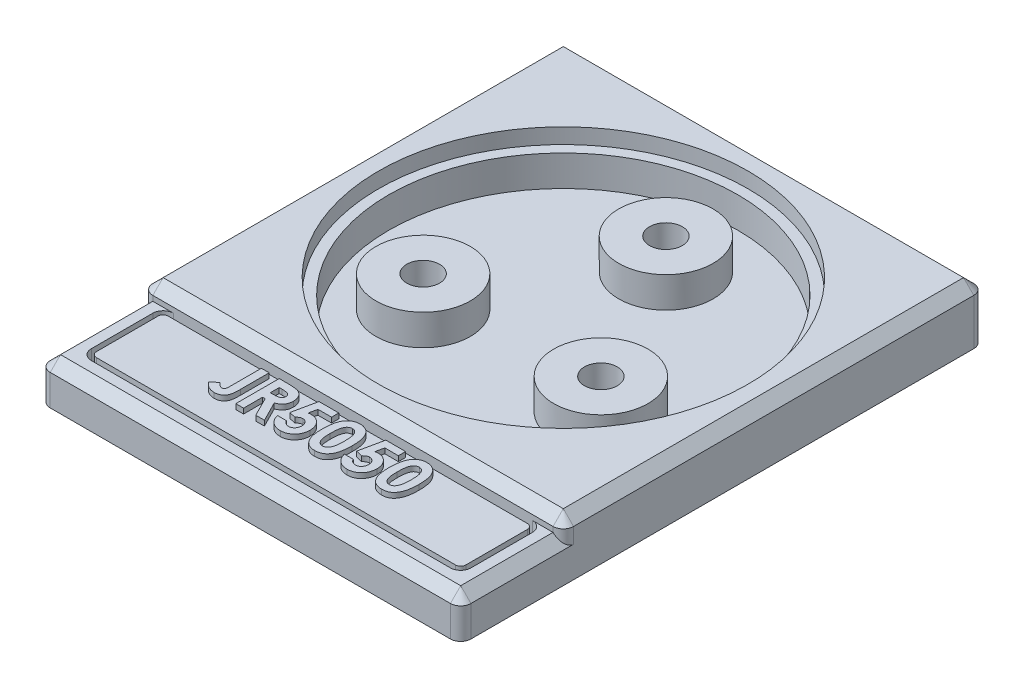
SolidWorks part; units mm, degrees
note: The reader was unsure of these and kept them because the rebuilt part matched: shared geometry of "Sketch3<3>", "Sketch3<4>".
other "Markup1"
sketch "Sketch7" plane through (-28, 7.5, 62.5) normal (-0.8225, 0.3134, 0.4747) x (0.5688, 0.4607, 0.6813)
material "PET"
ref_plane "Front Plane" through (0, 0, 0) normal (0, 0, 1) x (1, 0, 0)
ref_plane "Top Plane" through (0, 0, 0) normal (0, 1, 0) x (1, 0, 0)
ref_plane "Right Plane" through (0, 0, 0) normal (1, 0, 0) x (0, 0, -1)
sketch "base_sketch" plane through (0, 0, 0) normal (0, 1, 0) x (1, 0, 0)
  line L0 (0, 0) -> (0, 10) construction
  line L1 (-12.5, 12.5) -> (12.5, 12.5) construction
  line L2 (-12.5, 12.5) -> (-12.5, -12.5) construction
  line L3 (-12.5, -12.5) -> (12.5, -12.5) construction
  line L4 (12.5, 12.5) -> (12.5, -12.5) construction
  line L5 (-12.5, 12.5) -> (12.5, -12.5) construction
  line L6 (-12.5, -12.5) -> (12.5, 12.5) construction
  line L7 (-18, 18) -> (18, 18) construction
  line L8 (-18, 18) -> (-18, -18) construction
  line L9 (-18, -18) -> (18, -18) construction
  line L10 (18, 18) -> (18, -18) construction
  line L11 (-18, 18) -> (18, -18) construction
  line L12 (-18, -18) -> (18, 18) construction
  circle A0 centre (-12.5, 12.5) radius 1.6 construction
  circle A1 centre (12.5, 12.5) radius 1.6 construction
  circle A2 centre (-12.5, -12.5) radius 1.6 construction
  circle A3 centre (12.5, -12.5) radius 1.6 construction
  circle A4 centre (0, 0) radius 18 construction
  circle A5 centre (0, 10) radius 1.6 construction
  circle A6 centre (8.6603, -5) radius 1.6 construction
  circle A7 centre (-8.6603, -5) radius 1.6 construction
  point P0 (0, 0)
  point P11 (0, 0)
  point P20 (-10.4697, -3.1895)
  point P21 (0, 0)
  point P25 (0, 0)
  point P26 (0, 6.9336)
  dimension "D1" = 3.2
  dimension "D6" = 36
  dimension "D2" = 25
  dimension "D3" = 36
  dimension "D4" = 36
  dimension "D5" = 25
  dimension "D8" = 10
  dimension "D7" = 3
sketch "Sketch3" plane through (0, 0, 0) normal (0, 1, 0) x (1, 0, 0)
  line L14 (-17.5, -17.5) -> (17.5, -17.5)
  line L15 (17.5, -17.5) -> (17.5, 17.5)
  line L16 (17.5, 17.5) -> (-17.5, 17.5)
  line L17 (-17.5, 17.5) -> (-17.5, -17.5)
  line L18 (-17.5, -17.5) -> (17.5, -17.5) construction
  line L19 (17.5, -17.5) -> (17.5, 17.5) construction
  line L20 (17.5, 17.5) -> (-17.5, 17.5) construction
  line L21 (-17.5, 17.5) -> (-17.5, -17.5) construction
  line L28 (-20.5, 20.5) -> (-20.5, -20.5)
  line L29 (-20.5, -20.5) -> (20.5, -20.5)
  line L30 (20.5, -20.5) -> (20.5, 20.5)
  line L31 (20.5, 20.5) -> (-20.5, 20.5)
  line L32 (-18.5, -18.5) -> (18.5, -18.5)
  line L33 (18.5, -18.5) -> (18.5, 18.5)
  line L34 (18.5, 18.5) -> (-18.5, 18.5)
  line L35 (-18.5, 18.5) -> (-18.5, -18.5)
  line L36 (-18.5, -18.5) -> (18.5, -18.5)
  line L37 (18.5, -18.5) -> (18.5, 18.5)
  line L38 (18.5, 18.5) -> (-18.5, 18.5)
  line L39 (-18.5, 18.5) -> (-18.5, -18.5)
  line L40 (-20.5, -20.5) -> (-20.5, -30.5)
  line L41 (-20.5, -30.5) -> (20.5, -30.5)
  line L42 (20.5, -30.5) -> (20.5, -20.5)
  line L43 (-18.5, -20.5) -> (-18.5, -28.5)
  line L44 (-18.5, -28.5) -> (18.5, -28.5)
  line L45 (18.5, -28.5) -> (18.5, -20.5)
  circle A0 centre (0, 0) radius 18 construction
  circle A1 centre (0, 0) radius 18
  circle A2 centre (0, 0) radius 17
  dimension "D4" = 10
  dimension "D6" = 1
  dimension "D1" = 0.5
  dimension "D2" = 0.5
  dimension "D3" = 2
  dimension "D5" = 2
extrude "Boss-Extrude1" add sketch "Sketch3" along normal blind 1 contours L20 L21 L18 L19 | L30 L31 L28 L29 L39 L38 L37 L36 | L38 L39 L36 L37 A1 | A1 A2 | A2 | L44 L45 L29 L43 | L45 L44 L43 L29 L40 L41 L42
extrude "Boss-Extrude2" add sketch "Sketch3<3>" along normal blind 3 from surface at 1 contours L45 L44 L43 L29 L40 L41 L42 | L30 L31 L28 L29 L39 L38 L37 L36 | L38 L39 L36 L37 L21 L20 L19 L18 | A1 A2
sketch "Sketch3<3>" plane through (0, 0, 0) normal (0, 1, 0) x (1, 0, 0) same geometry as "Sketch3"
extrude "Boss-Extrude3" add sketch "Sketch3<4>" along normal blind 1.5 from surface at 4 contours L30 L31 L28 L29 L39 L38 L37 L36 | L38 L39 L36 L37 A1 starting at face at (0, 4, 24.5)
sketch "Sketch3<4>" plane through (0, 0, 0) normal (0, 1, 0) x (1, 0, 0) same geometry as "Sketch3"
sketch "Sketch4" plane through (0, 1, 0) normal (0, 1, 0) x (1, 0, 0)
  line L4 (-18.5, -28.5) -> (18.5, -28.5)
  line L5 (-18.5, -28.5) -> (18.5, -28.5)
  line L6 (18.5, -28.5) -> (18.5, -20.5)
  line L7 (18.5, -28.5) -> (18.5, -20.5)
  line L12 (18.5, -20.5) -> (-18.5, -20.5)
  line L13 (18.5, -20.5) -> (-18.5, -20.5)
  line L14 (-18.5, -20.5) -> (-18.5, -28.5)
  line L15 (-18.5, -20.5) -> (-18.5, -28.5)
  circle A0 centre (-12.5, -12.5) radius 1.6 construction
  circle A1 centre (12.5, -12.5) radius 1.6 construction
  circle A2 centre (12.5, 12.5) radius 1.6 construction
  circle A3 centre (-12.5, 12.5) radius 1.6 construction
  circle A4 centre (-12.5, -12.5) radius 1.6 construction
  circle A5 centre (12.5, -12.5) radius 1.6 construction
  circle A6 centre (12.5, 12.5) radius 1.6 construction
  circle A7 centre (-12.5, 12.5) radius 1.6 construction
  circle A8 centre (-12.5, 12.5) radius 4.6 construction
  circle A9 centre (12.5, 12.5) radius 4.6 construction
  circle A10 centre (12.5, -12.5) radius 4.6 construction
  circle A11 centre (-12.5, -12.5) radius 4.6 construction
  circle A12 centre (-8.6603, -5) radius 1.6 construction
  circle A13 centre (8.6603, -5) radius 1.6 construction
  circle A14 centre (0, 10) radius 1.6 construction
  circle A15 centre (-8.6603, -5) radius 1.6
  circle A16 centre (8.6603, -5) radius 1.6
  circle A17 centre (0, 10) radius 1.6
  circle A18 centre (0, 10) radius 4.6
  circle A19 centre (-8.6603, -5) radius 4.6
  circle A20 centre (8.6603, -5) radius 4.6
  dimension "D1" = 0
  dimension "D2" = 3
  dimension "D3" = 3
extrude "Boss-Extrude4" add sketch "Sketch4" along normal up to surface (3 mm away) up to face at (0, 4, 17)
fillet "Fillet1" radius 1 10 edges at (-18.5, 2.5, 28.5) (18.5, 2.5, 28.5) (18.5, 2.5, 20.5) (20.5, 2, 30.5) (-20.5, 2, 30.5) (-18.5, 2.5, 20.5) (20.5, 4.75, 20.5) (-20.5, 4.75, 20.5) (-20.5, 2.75, -20.5) (20.5, 2.75, -20.5)
chamfer "Chamfer1" distance 1 angle 45 13 edges at (-20.5, 5.5, 0) (-20.2071, 5.5, 20.2071) (-20.2071, 5.5, -20.2071) (0, 5.5, 20.5) (0, 5.5, -20.5) (20.2071, 5.5, 20.2071) (20.2071, 5.5, -20.2071) (20.5, 5.5, 0) (-20.5, 4, 24.5) (-20.2071, 4, 30.2071) (0, 4, 30.5) (20.2071, 4, 30.2071) (20.5, 4, 24.5)
sketch "Sketch5" plane through (0, 1, 0) normal (0, 1, 0) x (1, 0, 0)
  line L0 (-18, -21.5) -> (-18, -27.5)
  line L1 (-17.5, -28) -> (17.5, -28)
  line L2 (18, -27.5) -> (18, -21.5)
  line L3 (17.5, -21) -> (-17.5, -21)
  line L4 (-18.5, -21.5) -> (-18.5, -27.5)
  line L5 (-17.5, -28.5) -> (17.5, -28.5)
  line L6 (18.5, -27.5) -> (18.5, -21.5)
  line L7 (17.5, -20.5) -> (-17.5, -20.5)
  line L8 (-18.5, -21.5) -> (-18.5, -27.5) construction
  line L9 (-17.5, -28.5) -> (17.5, -28.5) construction
  line L10 (18.5, -27.5) -> (18.5, -21.5) construction
  line L11 (17.5, -20.5) -> (-17.5, -20.5) construction
  arc A0 (-18, -27.5) -> (-17.5, -28) centre (-17.5, -27.5) ccw
  arc A1 (17.5, -28) -> (18, -27.5) centre (17.5, -27.5) ccw
  arc A2 (18, -21.5) -> (17.5, -21) centre (17.5, -21.5) ccw
  arc A3 (-17.5, -21) -> (-18, -21.5) centre (-17.5, -21.5) ccw
  arc A4 (-18.5, -27.5) -> (-17.5, -28.5) centre (-17.5, -27.5) ccw
  arc A5 (17.5, -28.5) -> (18.5, -27.5) centre (17.5, -27.5) ccw
  arc A6 (18.5, -21.5) -> (17.5, -20.5) centre (17.5, -21.5) ccw
  arc A7 (-17.5, -20.5) -> (-18.5, -21.5) centre (-17.5, -21.5) ccw
  arc A8 (-18.5, -27.5) -> (-17.5, -28.5) centre (-17.5, -27.5) ccw construction
  arc A9 (17.5, -28.5) -> (18.5, -27.5) centre (17.5, -27.5) ccw construction
  arc A10 (18.5, -21.5) -> (17.5, -20.5) centre (17.5, -21.5) ccw construction
  arc A11 (-17.5, -20.5) -> (-18.5, -21.5) centre (-17.5, -21.5) ccw construction
  dimension "D1" = 0
  dimension "D2" = 0.5
extrude "Boss-Extrude5" add sketch "Sketch5" along normal up to surface (2.5 mm away) from offset 0.5 separate body up to face at (0, 4, 24.6667)
sketch "Sketch6" plane through (0, 4, 0) normal (0, 1, 0) x (1, 0, 0)
  line L0 (-18, -24.5) -> (18, -24.5) construction
  line L1 (-18, -27.5) -> (-18, -21.5) construction
  line L2 (18, -21.5) -> (18, -27.5) construction
  line L3 (0, -21) -> (0, -28) construction
  line L4 (-17.5, -21) -> (17.5, -21) construction
  line L5 (17.5, -28) -> (-17.5, -28) construction
  line L6 (-18, -25.5959) -> (18, -25.5959) construction
  text T0 "JR5050\r\n" font "Century Gothic" height in points 16
  point P12 (0, -24.5)
extrude "Boss-Extrude6" add sketch "Sketch6" along normal blind 0.5
